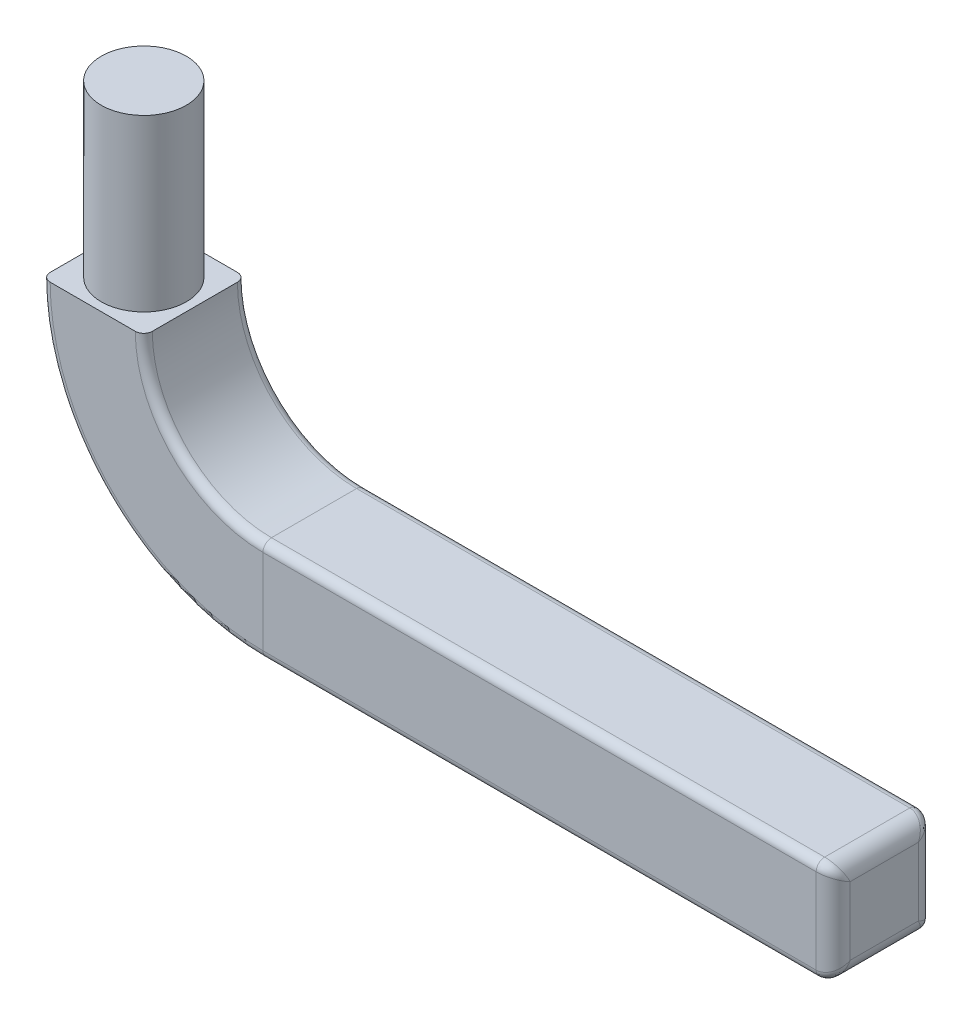
SolidWorks part; units mm, degrees
ref_plane "Přední rovina" through (0, 0, 0) normal (0, 0, 1) x (1, 0, 0)
ref_plane "Horní rovina" through (0, 0, 0) normal (0, 1, 0) x (1, 0, 0)
ref_plane "Pravá rovina" through (0, 0, 0) normal (1, 0, 0) x (0, 0, -1)
sketch "Skica1" plane through (0, 0, 0) normal (0, 0, 1) x (1, 0, 0)
  line L0 (-0.005, 0) -> (0.095, 0)
  line L3 (-0.005, 0) -> (-3.255, 0)
  line L4 (-4.255, 2) -> (-4.255, 1)
  arc A0 (-3.255, 0) -> (-4.255, 1) centre (-3.255, 1) cw
  point P0 (-2.13, 1)
  dimension "D1" = 0.1
  dimension "D3" = 1
sketch "Skica2" plane through (0, 0, 0) normal (1, 0, 0) x (0, 0, -1)
  line L1 (-0.25, 0.3) -> (0.25, 0.3)
  line L2 (-0.3, 0.25) -> (-0.3, -0.25)
  line L3 (-0.25, -0.3) -> (0.25, -0.3)
  line L4 (0.3, 0.25) -> (0.3, -0.25)
  arc A0 (-0.3, -0.25) -> (-0.25, -0.3) centre (-0.25, -0.25) ccw
  arc A1 (0.25, -0.3) -> (0.3, -0.25) centre (0.25, -0.25) ccw
  arc A2 (0.25, 0.3) -> (0.3, 0.25) centre (0.25, 0.25) cw
  arc A3 (-0.25, 0.3) -> (-0.3, 0.25) centre (-0.25, 0.25) ccw
  point P0 (0, 0)
  dimension "D3" = 0.05
sweep "Táhnout po křivce3" add profiles "Skica2" path "Skica1"
sketch "Skica13" plane through (0, 2, 0) normal (0, 1, 0) x (1, 0, 0)
  line L0 (-4.005, -0.3) -> (-4.505, -0.3) construction
  line L2 (-3.955, 0.25) -> (-3.955, -0.25) construction
  line L4 (-3.905, 0.35) -> (-4.605, 0.35)
  line L5 (-3.905, 0.35) -> (-3.905, -0.35)
  line L6 (-3.905, -0.35) -> (-4.605, -0.35)
  line L7 (-4.605, 0.35) -> (-4.605, -0.35)
  line L8 (-3.905, 0.35) -> (-4.605, -0.35) construction
  line L9 (-3.905, -0.35) -> (-4.605, 0.35) construction
  circle A0 centre (-4.255, 0) radius 0.25
  dimension "D1" = 0.5
  dimension "D2" = 0.3
  dimension "D3" = 0.3
  dimension "D4" = 0.7
  dimension "D5" = 0.7
extrude "Odebrat vysunutím2" cut sketch "Skica13" against normal blind 1
fillet "Zaoblit1" radius 0.1 8 edges at (0.095, -0.2854, 0.2854) (0.095, -0.2854, -0.2854) (0.095, 0.2854, -0.2854) (0.095, 0.2854, 0.2854) (0.095, 0.3, 0) (0.095, 0, -0.3) (0.095, -0.3, 0) (0.095, 0, 0.3)
